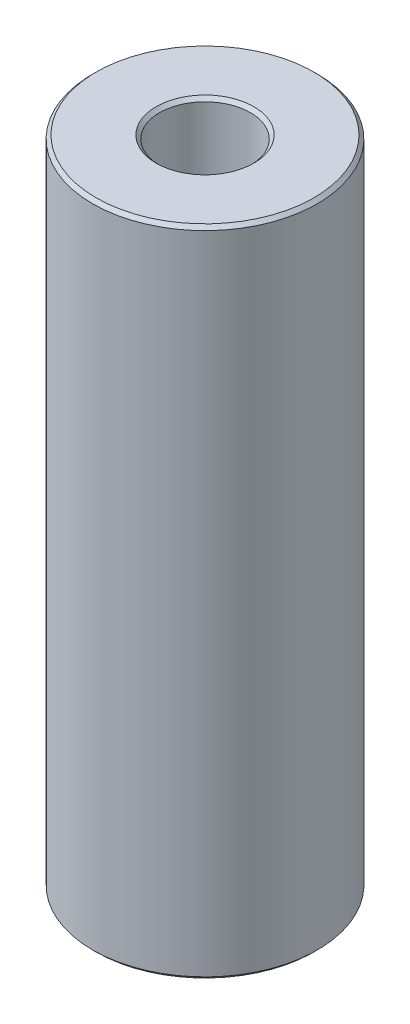
SolidWorks part; units mm, degrees
ref_plane "Front Plane" through (0, 0, 0) normal (0, 0, 1) x (1, 0, 0)
ref_plane "Top Plane" through (0, 0, 0) normal (0, 1, 0) x (1, 0, 0)
ref_plane "Right Plane" through (0, 0, 0) normal (1, 0, 0) x (0, 0, -1)
sketch "Sketch1" plane through (0, 0, 0) normal (0, 1, 0) x (1, 0, 0)
  circle A0 centre (0, 0) radius 55
  dimension "SLEEVE_OD" = 110
extrude "Boss-Extrude1" add sketch "Sketch1" along normal blind 319.6978
sketch "Sketch2" plane through (0, 0, 0) normal (0, 1, 0) x (1, 0, 0)
  circle A0 centre (0, 0) radius 22.2546
  dimension "BORE_D" = 44.5092
extrude "Cut-Extrude1" cut sketch "Sketch2" along normal through all
chamfer "Chamfer1" distance 1.6878 angle 45 4 edges at (0, 319.6978, 22.2546) (0, 0, 22.2546) (0, 0, 55) (0, 319.6978, 55)
